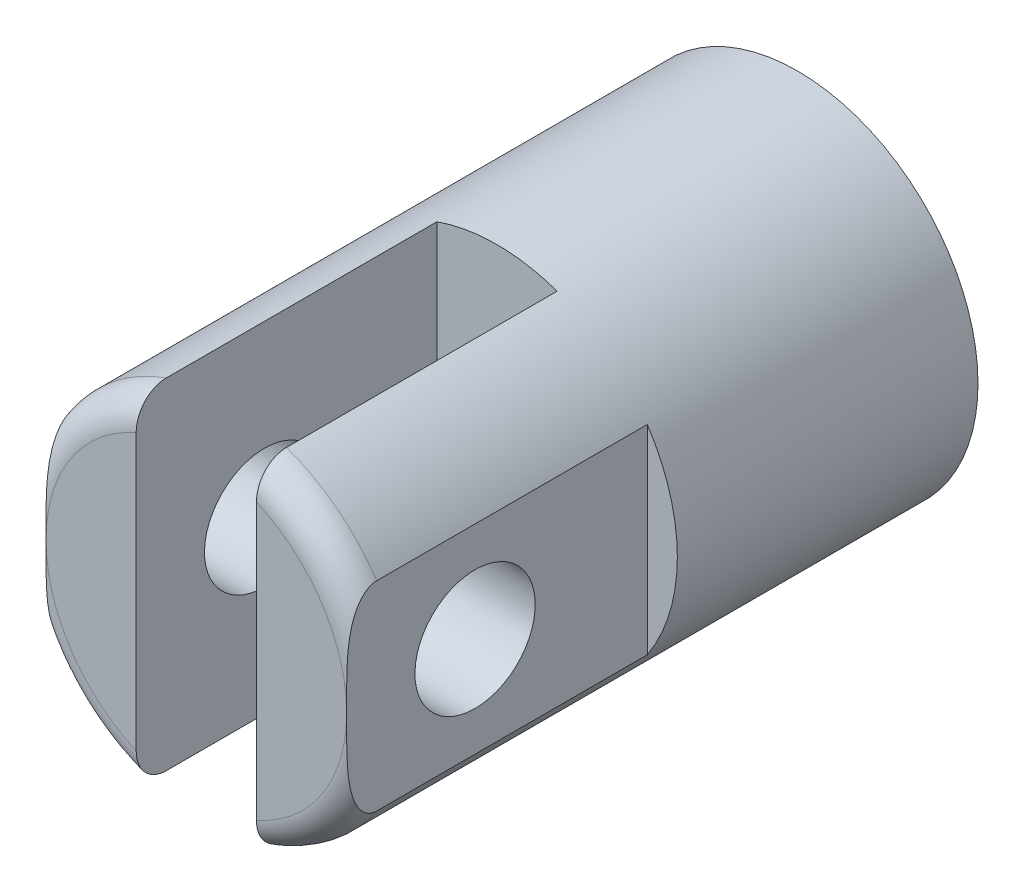
SolidWorks part; units mm, degrees
ref_plane "Спереди" through (0, 0, 0) normal (0, 0, 1) x (1, 0, 0)
ref_plane "Сверху" through (0, 0, 0) normal (0, 1, 0) x (1, 0, 0)
ref_plane "Справа" through (0, 0, 0) normal (1, 0, 0) x (0, 0, -1)
sketch "Эскиз1" plane through (0, 0, 0) normal (0, 0, 1) x (1, 0, 0)
  circle A0 centre (0, 0) radius 2
  circle A1 centre (0, 0) radius 6
extrude "Вытянуть1" add sketch "Эскиз1" along normal blind 10
sketch "Эскиз2" plane through (0, 0, 10) normal (0, 0, 1) x (1, 0, 0)
  line L0 (0, 0) -> (0, 6.5431) construction
  line L1 (-2, 8.6396) -> (-2, -10.6676) construction
  line L2 (-5, 6.7839) -> (-5, -6.4437) construction
  line L3 (-5, 3.3166) -> (-5, -3.3166)
  line L4 (-2, 5.6569) -> (-2, -5.6569)
  line L5 (2, 5.6569) -> (2, -5.6569)
  line L6 (5, 3.3166) -> (5, -3.3166)
  arc A0 (-5, 3.3166) -> (-2, 5.6569) centre (0, 0) cw
  circle A1 centre (0, 0) radius 6 construction
  arc A2 (-5, -3.3166) -> (-2, -5.6569) centre (0, 0) ccw
  arc A3 (5, -3.3166) -> (2, -5.6569) centre (0, 0) cw
  arc A4 (5, 3.3166) -> (2, 5.6569) centre (0, 0) ccw
  dimension "D1" = 2
  dimension "D2" = 3
extrude "Вытянуть2" add sketch "Эскиз2" along normal blind 10
sketch "Эскиз3" plane through (-5, 0, 0) normal (-1, 0, 0) x (0, 0, 1)
  circle A0 centre (15.7281, 0) radius 2
extrude "Вытянуть3" cut sketch "Эскиз3" against normal through all
fillet "Скругление1" radius 1 4 edges at (-3.6904, -4.7308, 20) (3.6904, -4.7308, 20) (3.6904, 4.7308, 20) (-3.6904, 4.7308, 20)
